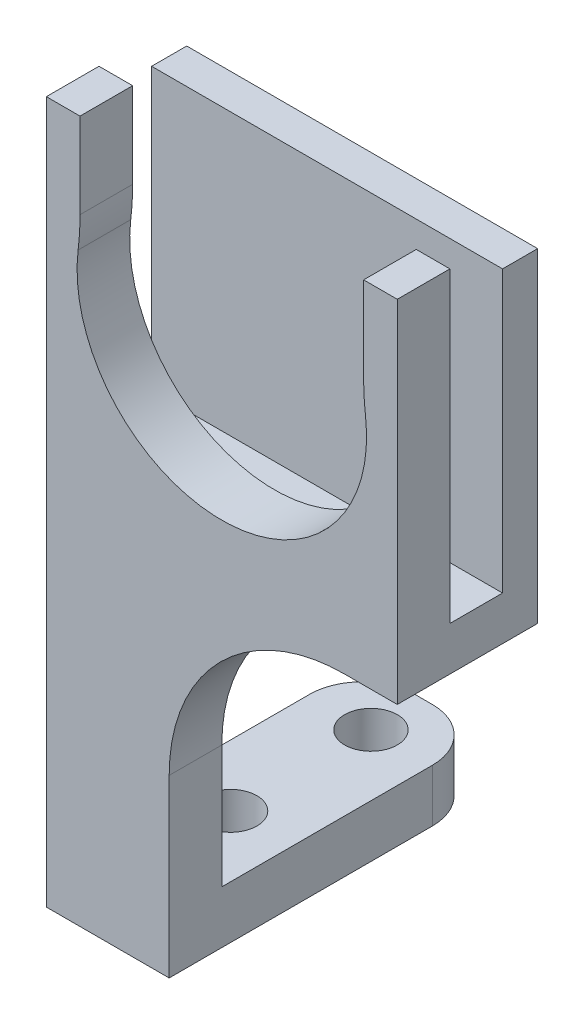
SolidWorks part; units mm, degrees
ref_plane "Front Plane" through (0, 0, 0) normal (0, 0, 1) x (1, 0, 0)
ref_plane "Top Plane" through (0, 0, 0) normal (0, 1, 0) x (1, 0, 0)
ref_plane "Right Plane" through (0, 0, 0) normal (1, 0, 0) x (0, 0, -1)
sketch "Sketch1" plane through (0, 0, 0) normal (0, 0, 1) x (1, 0, 0)
  line L0 (18.0821, 20) -> (20, 20)
  line L1 (0, 0) -> (20, 0)
  line L2 (0, 0) -> (0, 20)
  line L3 (0, 20) -> (1.9179, 20)
  line L4 (20, 0) -> (20, 20)
  line L5 (1.9179, 20) -> (1.9179, 14)
  line L6 (18.0821, 20) -> (18.0821, 14)
  arc A1 (1.9179, 14) -> (18.0821, 14) centre (10, 12.3441) ccw
  dimension "D3" = 6
  dimension "D5" = 8.25
  dimension "D1" = 20
  dimension "D2" = 20
  dimension "D4" = 6
extrude "Boss-Extrude1" add sketch "Sketch1" along normal blind 3 contours L0 L4 L1 L2 L3 L5 A1 L6
sketch "Sketch2" plane through (0, 0, 0) normal (0, 0, -1) x (-1, 0, 0)
  line L0 (0, 0) -> (0, 20) construction
  line L1 (-20, 0) -> (0, 0)
  line L2 (-20, 0) -> (-20, 2.5)
  line L3 (-20, 2.5) -> (0, 2.5)
  line L4 (0, 0) -> (0, 2.5)
  dimension "D1" = 2.5
extrude "Boss-Extrude2" add sketch "Sketch2" along normal blind 5
sketch "Sketch3" plane through (0, 2.5, 0) normal (0, 1, 0) x (1, 0, 0)
  line L0 (0, 5) -> (0, 0) construction
  line L1 (20, 5) -> (0, 5)
  line L2 (20, 5) -> (20, 3)
  line L3 (20, 3) -> (0, 3)
  line L4 (0, 5) -> (0, 3)
  dimension "D1" = 2
extrude "Boss-Extrude3" add sketch "Sketch3" along normal blind 16
fillet "Fillet1" radius 15 2 edges at (18.0821, 14, 1.5) (1.9179, 14, 1.5)
sketch "Sketch4" plane through (0, 0, 0) normal (0, -1, 0) x (1, 0, 0)
  line L1 (7, -5) -> (0, -5)
  line L2 (7, -5) -> (7, 3)
  line L3 (7, 3) -> (0, 3)
  line L4 (0, -5) -> (0, 3)
  dimension "D1" = 7
extrude "Boss-Extrude4" add sketch "Sketch4" along normal blind 20
sketch "Sketch5" plane through (0, 0, -5) normal (0, 0, -1) x (-1, 0, 0)
  line L4 (-7, -17) -> (0, -17)
  line L5 (-7, -20) -> (0, -20)
  line L6 (-7, -20) -> (-7, -17)
  line L7 (-7, -20) -> (-7, 0) construction
  line L9 (0, -20) -> (0, -17)
  line L10 (0, -20) -> (0, 18.5) construction
extrude "Boss-Extrude5" add sketch "Sketch5" along normal blind 10 contours L5 L9 L4 L6
fillet "Fillet2" radius 10 1 edges at (7, 0, -1)
sketch "Sketch6" plane through (0, -17, 0) normal (0, 1, 0) x (1, 0, 0)
  line L3 (7, 15) -> (0, 15) construction
  circle A0 centre (3.5, 12) radius 1.5
  circle A1 centre (3.5, 4) radius 1.5
  point P6 (0, 0)
  dimension "D1" = 3
  dimension "D2" = 3
  dimension "D3" = 3
  dimension "D4" = 8
sketch "Sketch7" plane through (0, 0, 0) normal (-1, 0, 0) x (0, 0, 1)
  line L0 (-5, -17) -> (-5, 18.5) construction
  line L1 (-5, 0) -> (0, 0)
  line L2 (-5, 0) -> (-5, -17)
  line L3 (-5, -17) -> (0, -17)
  line L4 (0, 0) -> (0, -17)
  line L5 (-5, -17) -> (-15, -17) construction
  line L6 (-3, 2.5) -> (0, 2.5) construction
  line L7 (3, -20) -> (3, 20) construction
  dimension "D1" = 2.5
  dimension "D2" = 3
extrude "Cut-Extrude1" cut sketch "Sketch7" against normal through all
fillet "Fillet3" radius 5 1 edges at (8.5, 0, 0)
extrude "Cut-Extrude2" cut sketch "Sketch6" against normal blind 10
fillet "Fillet4" radius 3 2 edges at (7, -18.5, -15) (0, -18.5, -15)
